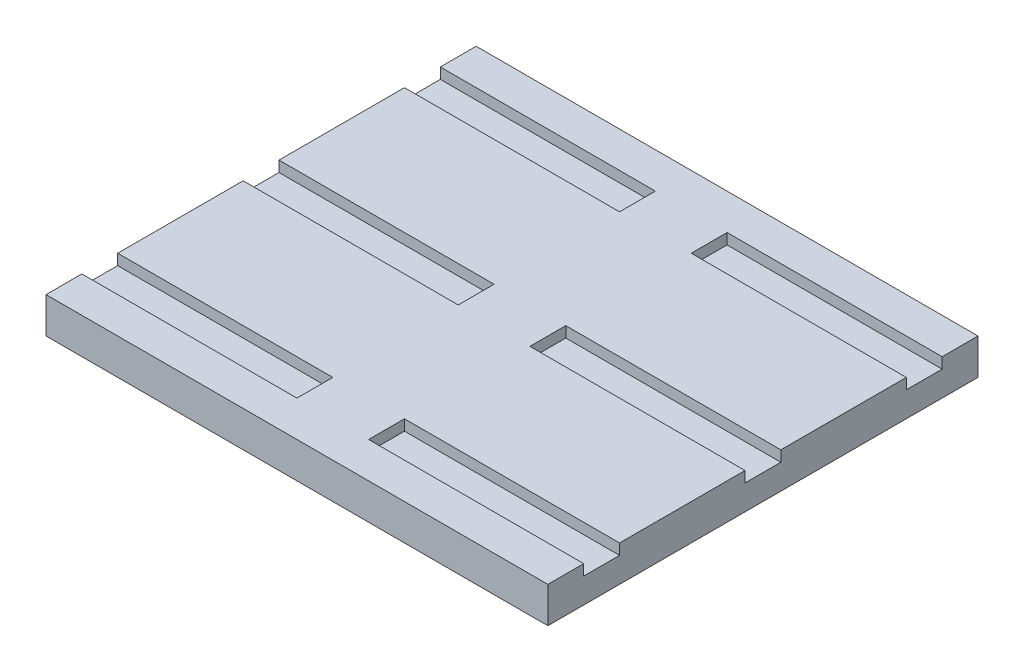
SolidWorks part; units mm, degrees
material "Acrylic (Medium-high impact)"
ref_plane "Front Plane" through (0, 0, 0) normal (0, 0, 1) x (1, 0, 0)
ref_plane "Top Plane" through (0, 0, 0) normal (0, 1, 0) x (1, 0, 0)
ref_plane "Right Plane" through (0, 0, 0) normal (1, 0, 0) x (0, 0, -1)
sketch "Sketch2" plane through (0, 0, 0) normal (0, 1, 0) x (1, 0, 0)
  line L1 (-88.9, 76.2) -> (88.9, 76.2)
  line L2 (-88.9, 76.2) -> (-88.9, -76.2)
  line L3 (-88.9, -76.2) -> (88.9, -76.2)
  line L4 (88.9, 76.2) -> (88.9, -76.2)
  line L5 (-88.9, 76.2) -> (88.9, -76.2) construction
  line L6 (-88.9, -76.2) -> (88.9, 76.2) construction
  point P0 (0, 0)
  dimension "D1" = 177.8
  dimension "D2" = 152.4
extrude "Boss-Extrude1" add sketch "Sketch2" along normal blind 12.7
sketch "Sketch4" plane through (88.9, 0, 0) normal (1, 0, 0) x (0, 0, -1)
  line L0 (-76.2, 12.7) -> (76.2, 12.7) construction
  line L1 (-63.5, 12.7) -> (-50.8, 12.7)
  line L2 (-63.5, 12.7) -> (-63.5, 8.89)
  line L3 (-63.5, 8.89) -> (-50.8, 8.89)
  line L4 (-50.8, 12.7) -> (-50.8, 8.89)
  line L5 (-76.2, 12.7) -> (-76.2, 0) construction
  dimension "D1" = 3.81
  dimension "D2" = 12.7
  dimension "D3" = 12.7
extrude "Cut-Extrude1" cut sketch "Sketch4" against normal blind 76.2
mirror "Mirror1" about plane through (0, 0, 0) normal (0, 0, 1) of "Cut-Extrude1"
sketch "Sketch5" plane through (88.9, 0, 0) normal (1, 0, 0) x (0, 0, -1)
  line L0 (-50.8, 12.7) -> (50.8, 12.7) construction
  line L1 (-6.35, 12.7) -> (6.35, 12.7)
  line L2 (-6.35, 12.7) -> (-6.35, 8.89)
  line L3 (-6.35, 8.89) -> (6.35, 8.89)
  line L4 (6.35, 12.7) -> (6.35, 8.89)
  point P6 (0, 8.89)
  dimension "D1" = 3.81
  dimension "D2" = 12.7
extrude "Cut-Extrude2" cut sketch "Sketch5" against normal blind 76.2
mirror "Mirror3" about plane through (0, 0, 0) normal (1, 0, 0) of "Cut-Extrude2", "Mirror1", "Cut-Extrude1"
